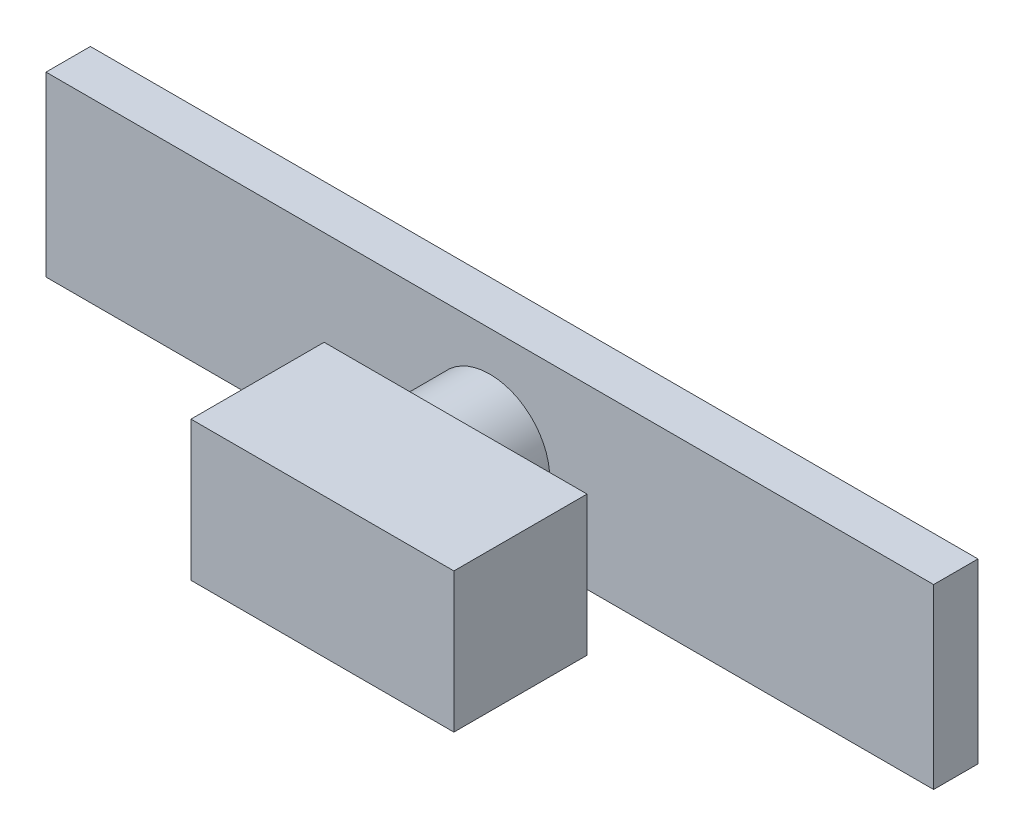
SolidWorks part; units mm, degrees
ref_plane "Front Plane" through (0, 0, 0) normal (0, 0, 1) x (1, 0, 0)
ref_plane "Top Plane" through (0, 0, 0) normal (0, 1, 0) x (1, 0, 0)
ref_plane "Right Plane" through (0, 0, 0) normal (1, 0, 0) x (0, 0, -1)
sketch "Sketch2" plane through (0, 0, 0) normal (0, 0, 1) x (1, 0, 0)
  line L1 (-47.8692, 21.2481) -> (206.1308, 21.2481)
  line L2 (-47.8692, 21.2481) -> (-47.8692, 8.5481)
  line L3 (-47.8692, 8.5481) -> (206.1308, 8.5481)
  line L4 (206.1308, 21.2481) -> (206.1308, 8.5481)
  dimension "D1" = 12.7
  dimension "D2" = 254
extrude "Boss-Extrude1" add sketch "Sketch2" along normal blind 50.8
sketch "Sketch3" plane through (0, 21.2481, 0) normal (0, 1, 0) x (1, 0, 0)
  circle A0 centre (79.1308, -28.4831) radius 17.1408
extrude "Boss-Extrude2" add sketch "Sketch3" along normal blind 19.05
sketch "Sketch4" plane through (0, 40.2981, 0) normal (0, 1, 0) x (1, 0, 0)
  line L1 (50.7675, -8.111) -> (126.0034, -8.111)
  line L2 (50.7675, -8.111) -> (50.7675, -48.0661)
  line L3 (50.7675, -48.0661) -> (126.0034, -48.0661)
  line L4 (126.0034, -8.111) -> (126.0034, -48.0661)
extrude "Boss-Extrude3" add sketch "Sketch4" along normal blind 38.1
scale "Scale2" scale about centroid uniform scaling yes scale factor 0.06
move or copy body "Body-Move/Copy1" bodies to move or copy 105 copy no rotation origin (0, 33.6669, 26.5501) rotation axis (1, 0, 0) rotation angle 90
move or copy body "Body-Move/Copy3" bodies to move or copy 106 copy no translate (-50.8, 0, -50.8)
scale "Scale5" scale about centroid uniform scaling yes scale factor 0.25
move or copy body "Body-Move/Copy6" bodies to move or copy 111 copy no translate (50.8, 0, 0)
